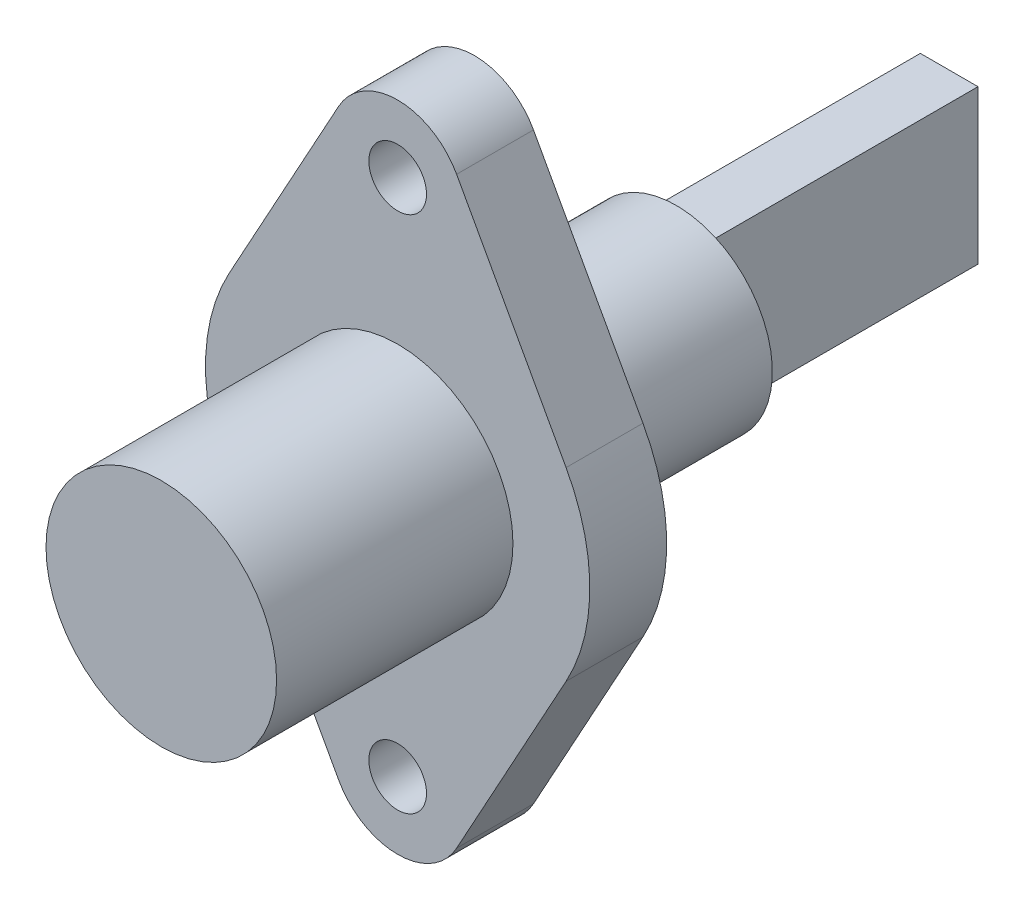
SolidWorks part; units mm, degrees
material "Custom Plastic"
ref_plane "X-Y Datum" through (0, 0, 0) normal (0, 0, 1) x (1, 0, 0)
ref_plane "X-Z Datum" through (0, 0, 0) normal (0, 1, 0) x (1, 0, 0)
ref_plane "Y-Z Datum" through (0, 0, 0) normal (1, 0, 0) x (0, 0, -1)
sketch "Sketch1" plane through (0, 0, 0) normal (0, 0, 1) x (1, 0, 0)
  line L0 (0, 17) -> (0, -17) construction
  line L1 (-10, 0) -> (10, 0) construction
  line L2 (-3.0676, 15.1852) -> (-8.7646, 4.8148)
  line L3 (3.0676, 15.1852) -> (8.7646, 4.8148)
  line L4 (3.0676, -15.1852) -> (8.7646, -4.8148)
  line L5 (-3.0676, -15.1852) -> (-8.7646, -4.8148)
  circle A0 centre (0, 0) radius 10
  circle A3 centre (0, 13.5) radius 3.5
  circle A4 centre (0, -13.5) radius 3.5
  circle A5 centre (0, 13.5) radius 1.5
  circle A6 centre (0, -13.5) radius 1.5
  point P4 (0, 0)
  point P8 (0, 0)
  dimension "D3" = 3
  dimension "D1" = 34
  dimension "D2" = 20
extrude "Boss-Extrude1" add sketch "Sketch1" along normal blind 4 contours A4 A6 | A0 A4 L4 | A0 | A3 A0 L3 | A3 A5 | A3 L2 A0 | L5 A4 A0 region at (-4.4007, 10.2822, 0) region at (0, 16.901, 0) region at (0, 0, 0) region at (4.4007, 10.2822, 0) region at (-4.4007, -10.2822, 0) region at (-2.9271, -11.7683, 0) region at (4.4007, -10.2822, 0)
sketch "Sketch2" plane through (0, 0, 4) normal (0, 0, 1) x (1, 0, 0)
  circle A0 centre (0, 0) radius 6
  dimension "D1" = 12
extrude "Boss-Extrude2" add sketch "Sketch2" along normal blind 12.3
sketch "Sketch3" plane through (0, 0, 0) normal (0, 0, -1) x (-1, 0, 0)
  circle A0 centre (0, 0) radius 7.5
  dimension "D1" = 15
extrude "Boss-Extrude3" add sketch "Sketch3" along normal blind 0.5
sketch "Sketch4" plane through (0, 0, -0.5) normal (0, 0, -1) x (-1, 0, 0)
  line L1 (-1.5, 4) -> (1.5, 4)
  line L2 (-1.5, 4) -> (-1.5, -4)
  line L3 (-1.5, -4) -> (1.5, -4)
  line L4 (1.5, 4) -> (1.5, -4)
  line L5 (-1.5, 4) -> (1.5, -4) construction
  line L6 (-1.5, -4) -> (1.5, 4) construction
  point P0 (0, 0)
  dimension "D1" = 8
  dimension "D2" = 3
extrude "Boss-Extrude4" add sketch "Sketch4" along normal blind 24.2
sketch "Sketch5" plane through (0, 0, -0.5) normal (0, 0, -1) x (-1, 0, 0)
  circle A0 centre (0, 0) radius 5
  dimension "D1" = 10
extrude "Boss-Extrude5" add sketch "Sketch5" along normal blind 10
